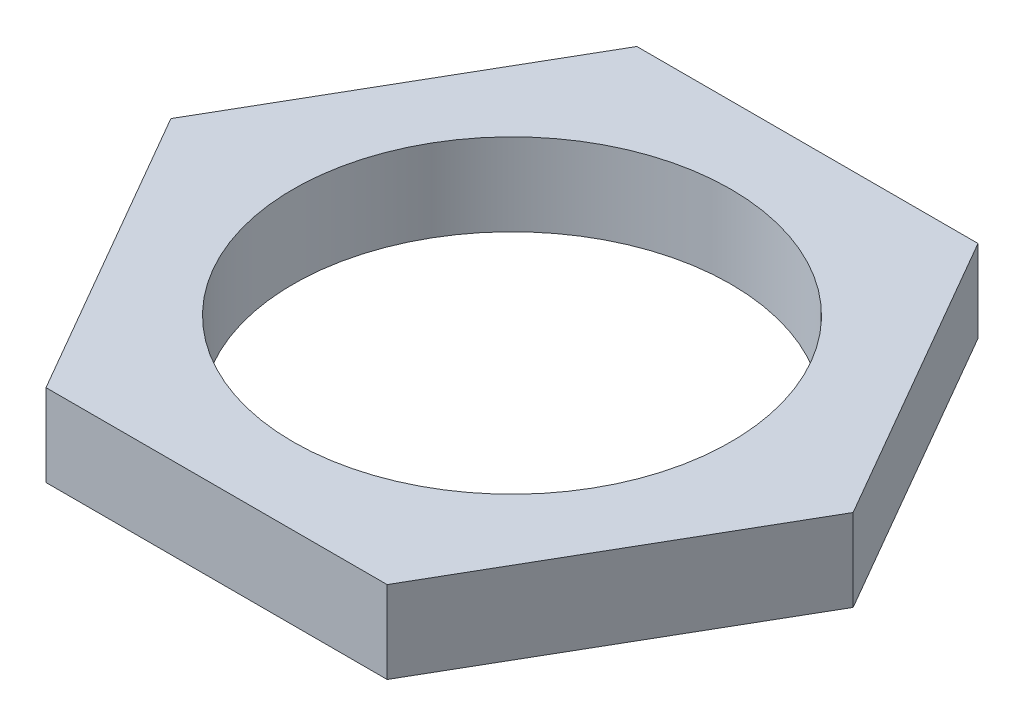
SolidWorks part; units mm, degrees
ref_plane "Front Plane" through (0, 0, 0) normal (0, 0, 1) x (1, 0, 0)
ref_plane "Top Plane" through (0, 0, 0) normal (0, 1, 0) x (1, 0, 0)
ref_plane "Right Plane" through (0, 0, 0) normal (1, 0, 0) x (0, 0, -1)
ref_plane "Nut Bottom" through (0, 17.2, 0) normal (0, 1, 0) x (1, 0, 0)
sketch "Nut Sketch" plane through (0, 17.2, 0) normal (0, 1, 0) x (1, 0, 0)
  line L0 (13.2791, 0) -> (6.6395, 11.5)
  line L1 (6.6395, 11.5) -> (-6.6395, 11.5)
  line L2 (-6.6395, 11.5) -> (-13.2791, 0)
  line L3 (-13.2791, 0) -> (-6.6395, -11.5)
  line L4 (-6.6395, -11.5) -> (6.6395, -11.5)
  line L5 (6.6395, -11.5) -> (13.2791, 0)
extrude "Nut" add sketch "Nut Sketch" along normal blind 3.2
ref_axis "Engine Axis" through (14.607, 0, 0) along (-1, 0, 0)
sketch "Bore Sketch" plane through (0, 0, 0) normal (0, 0, 1) x (1, 0, 0)
  line L0 (0, -100) -> (0, 200) construction
  line L1 (0, 16.2) -> (8.52, 16.2)
  line L2 (8.52, 16.2) -> (8.52, 21.4)
  line L3 (8.52, 21.4) -> (0, 21.4)
  line L4 (0, 21.4) -> (0, 16.2)
revolve "Bore" cut sketch "Bore Sketch" angle 360 about L0
